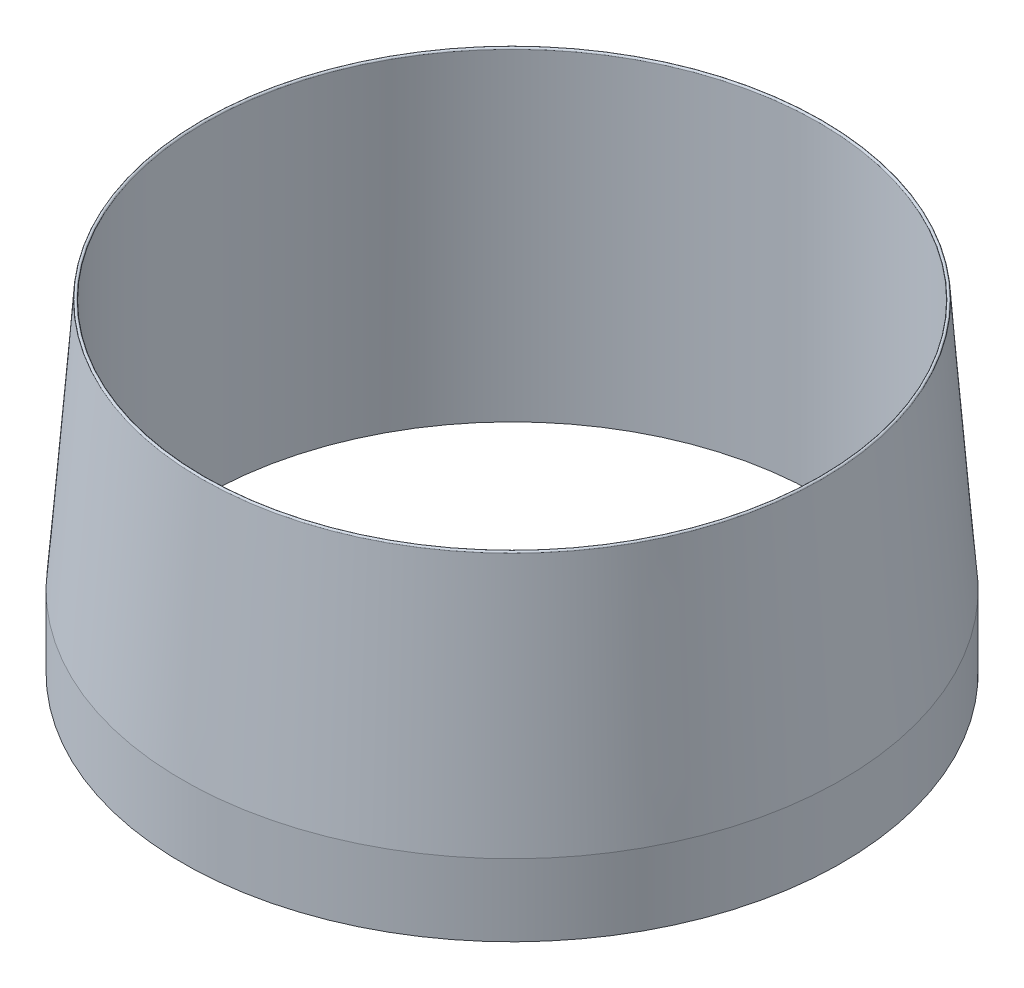
SolidWorks part; units mm, degrees
material "6061-T6 (SS)"
ref_plane "Front Plane" through (0, 0, 0) normal (0, 0, 1) x (1, 0, 0)
ref_plane "Top Plane" through (0, 0, 0) normal (0, 1, 0) x (1, 0, 0)
ref_plane "Right Plane" through (0, 0, 0) normal (1, 0, 0) x (0, 0, -1)
sketch "Sketch1" plane through (0, 0, 0) normal (0, 0, 1) x (1, 0, 0)
  line L0 (27.1145, 0) -> (29.083, 0)
  line L1 (29.083, 0) -> (29.083, 6.35)
  line L2 (29.083, 6.35) -> (27.1145, 31.75)
  line L3 (27.1145, 31.75) -> (27.1145, 0)
  dimension "D1" = 27.1145
  dimension "D2" = 29.083
  dimension "D3" = 6.35
  dimension "D4" = 31.75
ref_axis "Axis1" through (0, -0.9525, 0) along (0, 1, 0)
revolve "Revolve1" add sketch "Sketch1" angle 360 about axis through (0, -0.9525, 0) along (0, 1, 0)
fillet "Fillet1" radius 0.127 1 edges at (0, 31.75, -27.1145)
